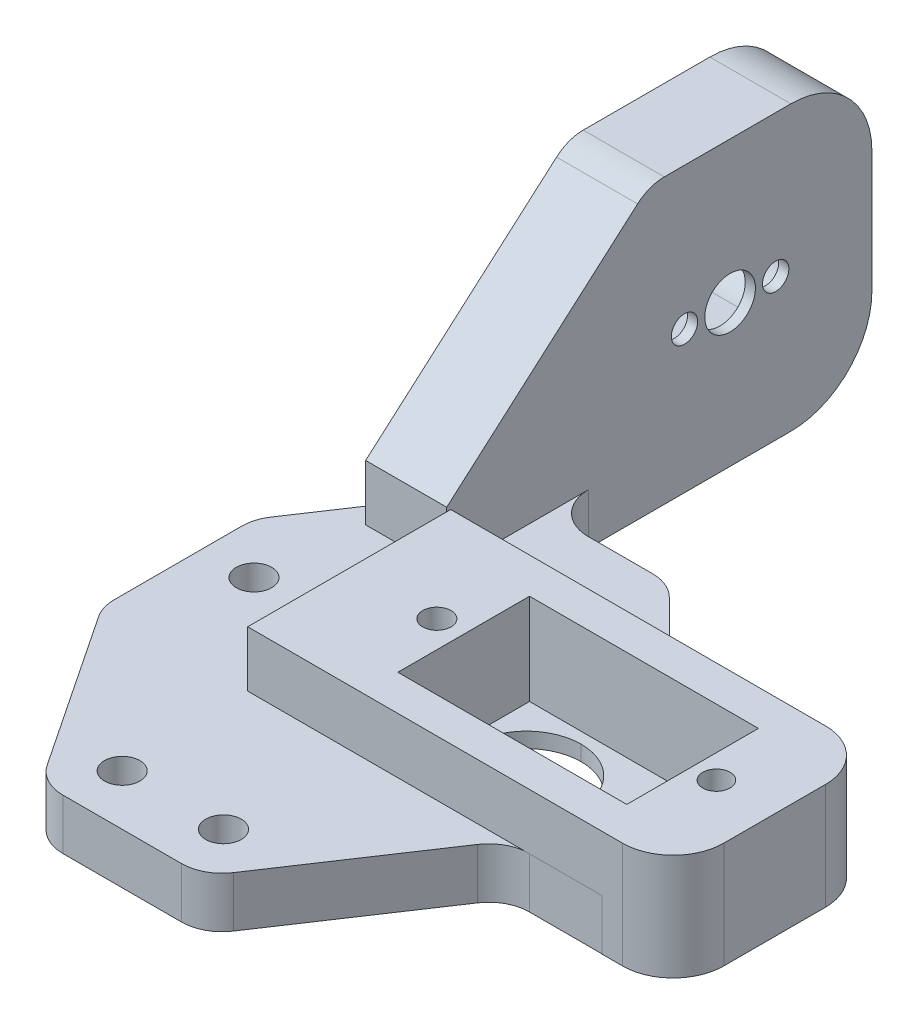
SolidWorks part; units mm, degrees
ref_plane "Front Plane" through (0, 0, 0) normal (0, 0, 1) x (1, 0, 0)
ref_plane "Top Plane" through (0, 0, 0) normal (0, 1, 0) x (1, 0, 0)
ref_plane "Right Plane" through (0, 0, 0) normal (1, 0, 0) x (0, 0, -1)
sketch "Sketch1" plane through (0, 0, 0) normal (0, 1, 0) x (1, 0, 0)
  line L0 (0, 0) -> (45, 0) construction
  line L1 (45, -10) -> (45, 10)
  line L2 (45, 10) -> (21, 10)
  line L3 (21, 10) -> (11.0015, 19.9985)
  line L4 (11.0015, 19.9985) -> (-4.9985, 19.9985)
  line L5 (-4.9985, 19.9985) -> (-14.9997, 4.9966)
  line L6 (-14.9997, 4.9966) -> (-14.9997, -10.0034)
  line L10 (-14.9997, -10.0034) -> (-2.9797, -28.0334)
  line L11 (-2.9797, -28.0334) -> (13.0203, -28.0334)
  line L16 (13.0203, -28.0334) -> (25.0425, -10)
  line L17 (25.0425, -10) -> (45, -10)
  point P6 (45, 0)
  dimension "D1" = 20
  dimension "D2" = 24
  dimension "D3" = 14.14
  dimension "D4" = 16
  dimension "D5" = 18.03
  dimension "D6" = 15
  dimension "D7" = 146.31
  dimension "D8" = 123.69
  dimension "D9" = 18.03
  dimension "D10" = 16
  dimension "D11" = 123.69
  dimension "D13" = 225
  dimension "D14" = 45
extrude "Boss-Extrude1" add sketch "Sketch1" along normal blind 5
sketch "Sketch2" plane through (0, 5, 0) normal (0, 1, 0) x (1, 0, 0)
  line L0 (45, 0) -> (-25.8429, 0) construction
  line L1 (45, -10) -> (45, 10) construction
  line L2 (-14.9997, 4.9966) -> (-14.9997, -10.0034) construction
  line L3 (-14.9997, -10.0034) -> (25.0425, -10) construction
  line L4 (5.0214, -10.0017) -> (5.0214, -23.0334) construction
  line L5 (10.0214, -23.0334) -> (0.0214, -23.0334)
  line L6 (-2.9797, -28.0334) -> (13.0203, -28.0334) construction
  line L8 (11.5, -5.4) -> (22.3, -5.4)
  line L9 (11.5, -5.4) -> (11.5, 5.4)
  line L10 (11.5, 5.4) -> (22.3, 5.4)
  line L11 (22.3, -5.4) -> (22.3, 5.4)
  line L12 (11.5, -5.4) -> (22.3, 5.4) construction
  line L13 (11.5, 5.4) -> (22.3, -5.4) construction
  circle A0 centre (-9.9997, 0) radius 1.75
  circle A1 centre (0.0214, -23.0334) radius 1.75
  circle A2 centre (10.0214, -23.0334) radius 1.75
  point P18 (5.0214, -23.0334)
  point P22 (16.9, 0)
  dimension "D2" = 3.5
  dimension "D5" = 3.5
  dimension "D1" = 5
  dimension "D3" = 10
  dimension "D4" = 5
  dimension "D6" = 22.7
  dimension "D7" = 10.8
  dimension "D8" = 10.8
extrude "Cut-Extrude1" cut sketch "Sketch2" against normal through all contours L8 L11 L10 L9 | A0 | A1 | A2 region at (-1.6791, 5, 23.0334) region at (10.0214, 5, 21.3329) region at (16.9, 5, 0) region at (-9.9997, 5, 0)
fillet "Fillet1" 2 edges at (11.5, 2.5, -5.4) (11.5, 2.5, 5.4) type full round first side face at (16.9, 2.5, -5.4) second side face at (16.9, 2.5, 5.4) middle face at (11.5, 2.5, 0)
fillet "Fillet2" 2 edges at (22.3, 2.5, -5.4) (22.3, 2.5, 5.4) type full round first side face at (19.6, 2.5, -5.4) second side face at (19.6, 2.5, 5.4) middle face at (22.3, 2.5, 0)
fillet "Fillet3" 2 edges at (45, 2.5, -10) (45, 2.5, 10) type full round first side face at (33, 2.5, -10) second side face at (35.0212, 2.5, 10) middle face at (45, 2.5, 0)
sketch "Sketch6" plane through (0, 5, 0) normal (0, 1, 0) x (1, 0, 0)
  line L0 (11.5, 0) -> (22.3, 0) construction
  line L2 (5.4, -6.5) -> (28.4, -6.5)
  line L3 (5.4, -6.5) -> (5.4, 6.5)
  line L4 (5.4, 6.5) -> (28.4, 6.5)
  line L5 (28.4, -6.5) -> (28.4, 6.5)
  line L6 (5.4, -6.5) -> (28.4, 6.5) construction
  line L7 (5.4, 6.5) -> (28.4, -6.5) construction
  line L8 (-0.6, -10.0211) -> (34.4, -10.0211)
  line L9 (-0.6, -10.0211) -> (-0.6, 10.0211)
  line L10 (-0.6, 10.0211) -> (34.4, 10.0211)
  line L11 (34.4, -10.0211) -> (34.4, 10.0211)
  line L12 (-0.6, -10.0211) -> (34.4, 10.0211) construction
  line L13 (-0.6, 10.0211) -> (34.4, -10.0211) construction
  arc A0 (16.9, 5.4) -> (16.9, -5.4) centre (16.9, 0) ccw construction
  arc A1 (16.9, -5.4) -> (16.9, 5.4) centre (16.9, 0) ccw construction
  point P8 (16.9, 0)
  point P13 (16.9, 0)
  dimension "D1" = 6
  dimension "D2" = 13
  dimension "D3" = 23
extrude "Boss-Extrude3" add sketch "Sketch6" along normal blind 5.5
sketch "Sketch7" plane through (0, 5, 0) normal (0, 1, 0) x (1, 0, 0)
  line L4 (5.4, 6.5) -> (5.4, -6.5)
  line L5 (5.4, -6.5) -> (28.4, -6.5)
  line L6 (28.4, -6.5) -> (28.4, 6.5)
  line L7 (28.4, 6.5) -> (5.4, 6.5)
  line L8 (5.4, 6.5) -> (5.4, -6.5)
  line L9 (5.4, -6.5) -> (28.4, -6.5)
  line L10 (28.4, -6.5) -> (28.4, 6.5)
  line L11 (28.4, 6.5) -> (5.4, 6.5)
  dimension "D1" = 0
extrude "Cut-Extrude3" cut sketch "Sketch7" against normal blind 3.5
sketch "Sketch8" plane through (0, 5, 0) normal (0, 1, 0) x (1, 0, 0)
  line L3 (34.4, 10) -> (34.4, -10)
  line L4 (34.4, -10) -> (35, -10)
  line L5 (35, 10) -> (34.4, 10)
  line L6 (34.4, 10) -> (34.4, -10)
  line L7 (34.4, -10) -> (35, -10)
  line L8 (35, 10) -> (34.4, 10)
  arc A1 (35, -10) -> (35, 10) centre (35, 0) ccw
  arc A2 (35, -10) -> (35, 10) centre (35, 0) ccw
  dimension "D1" = 0
extrude "Cut-Extrude4" cut sketch "Sketch8" against normal through all body kept at (25.0425, 0, 10)
sketch "Sketch9" plane through (0, 0, -19.9985) normal (0, 0, -1) x (-1, 0, 0)
  line L0 (-11.0015, 0) -> (4.9985, 0) construction
  line L1 (0.9985, 0) -> (8.9985, 0)
  line L2 (0.9985, 0) -> (0.9985, 28)
  line L3 (0.9985, 28) -> (8.9985, 28)
  line L4 (8.9985, 0) -> (8.9985, 28)
  line L5 (4.9985, 5) -> (4.9985, 0) construction
  dimension "D1" = 4
  dimension "D2" = 4
  dimension "D3" = 28
extrude "Boss-Extrude4" add sketch "Sketch9" along normal blind 32
sketch "Sketch11" plane through (-0.9985, 0, 0) normal (1, 0, 0) x (0, 0, -1)
  line L0 (10, 0) -> (19.9985, 0) construction
  line L1 (51.9985, 28) -> (51.9985, 0) construction
  line L2 (42.4985, 14) -> (33.4985, 14) construction
  circle A0 centre (37.9985, 14) radius 2.5
  circle A1 centre (33.4985, 14) radius 1.3
  circle A2 centre (42.4985, 14) radius 1.3
  point P9 (37.9985, 14)
  dimension "D1" = 5
  dimension "D5" = 2.6
  dimension "D2" = 14
  dimension "D3" = 14
  dimension "D4" = 9
extrude "Cut-Extrude5" cut sketch "Sketch11" against normal through all
fillet "Fillet6" radius 8 2 edges at (-4.9985, 0, -51.9985) (-4.9985, 28, -51.9985)
sketch "Sketch12" plane through (-8.9985, 0, 0) normal (-1, 0, 0) x (0, 0, 1)
  line L0 (-10.0211, 10.5) -> (-19.9985, 28)
  line L1 (-19.9985, 28) -> (-19.9985, 0)
  line L2 (-19.9985, 0) -> (-10, 0)
  line L3 (-10, 0) -> (-10.0211, 10.5)
extrude "Boss-Extrude5" add sketch "Sketch12" against normal up to surface (8 mm away) up to face at (-0.9985, 14, -43.7985)
sketch "Sketch13" plane through (-8.9985, 0, 0) normal (-1, 0, 0) x (0, 0, 1)
  line L0 (-40.4985, 14) -> (-35.4985, 14) construction
  line L2 (-44.9985, 10.5) -> (-30.9985, 10.5)
  line L3 (-44.9985, 10.5) -> (-44.9985, 17.5)
  line L4 (-44.9985, 17.5) -> (-30.9985, 17.5)
  line L5 (-30.9985, 10.5) -> (-30.9985, 17.5)
  line L6 (-44.9985, 10.5) -> (-30.9985, 17.5) construction
  line L7 (-44.9985, 17.5) -> (-30.9985, 10.5) construction
  circle A0 centre (-37.9985, 14) radius 2.5 construction
  point P5 (-37.9985, 14)
  dimension "D1" = 7
  dimension "D2" = 14
extrude "Cut-Extrude6" cut sketch "Sketch13" against normal blind 7
fillet "Fillet7" 2 edges at (-5.4985, 17.5, -44.9985) (-5.4985, 10.5, -44.9985) type full round first side face at (-5.4985, 17.5, -37.9985) second side face at (-5.4985, 10.5, -37.9985) middle face at (-5.4985, 14, -44.9985)
fillet "Fillet8" 2 edges at (-5.4985, 17.5, -30.9985) (-5.4985, 10.5, -30.9985) type full round first side face at (-5.4985, 17.5, -36.2485) second side face at (-5.4985, 10.5, -36.2485) middle face at (-5.4985, 14, -30.9985)
sketch "Sketch14" plane through (-8.9985, 0, 0) normal (-1, 0, 0) x (0, 0, 1)
  line L0 (-10.0211, 10.5) -> (-29.9985, 28)
  line L1 (-43.9985, 28) -> (-19.9985, 28) construction
  line L2 (-29.9985, 28) -> (-19.9985, 28)
  line L3 (-19.9985, 28) -> (-10.0211, 10.5)
  dimension "D1" = 10
extrude "Cut-Extrude7" cut sketch "Sketch14" against normal through all
fillet "Fillet9" radius 4 10 edges at (-0.9985, 2.5, -19.9985) (11.0015, 2.5, -19.9985) (21, 2.5, -10) (25.0425, 2.5, 10) (13.0203, 2.5, 28.0334) (-2.9797, 2.5, 28.0334) (-14.9997, 2.5, 10.0034) (-14.9997, 2.5, -4.9966) (-8.9985, 2.5, -13.9985) (-4.9985, 28, -29.9985)
sketch "Sketch15" plane through (0, 1.5, 0) normal (0, 1, 0) x (1, 0, 0)
  line L0 (5.4, -6.5) -> (28.4, -6.5) construction
  line L1 (5.4, 6.5) -> (10.7, 6.5)
  line L2 (5.4, 6.5) -> (5.4, -6.5)
  line L3 (5.4, -6.5) -> (10.7, -6.5)
  line L4 (10.7, 6.5) -> (10.7, -6.5)
  line L5 (5.4, 0) -> (10.7, 0) construction
  circle A0 centre (8.05, 0) radius 1.4
  dimension "D2" = 2.8
  dimension "D1" = 5.3
extrude "Boss-Extrude6" add sketch "Sketch15" along normal up to surface (9 mm away) up to face at (16.9, 10.5, 0)
sketch "Sketch16" plane through (0, 10.5, 0) normal (0, 1, 0) x (1, 0, 0)
  line L0 (34.4, 10.0211) -> (41.4, 10.0211)
  line L1 (34.4, -10.0211) -> (41.4, -10.0211)
  line L2 (41.4, -10.0211) -> (41.4, 10.0211)
  line L3 (34.4, -10.0211) -> (34.4, 10.0211) construction
  line L4 (34.4, -10.0211) -> (34.4, 10.0211)
  dimension "D1" = 7
extrude "Boss-Extrude7" add sketch "Sketch16" against normal up to surface (10.5 mm away) up to face at (5.3358, 0, -3.5695)
sketch "Sketch17" plane through (0, 10.5, 0) normal (0, 1, 0) x (1, 0, 0)
  line L0 (8.05, 0) -> (35.65, 0) construction
  circle A0 centre (35.65, 0) radius 1.35
  dimension "D2" = 2.7
  dimension "D1" = 27.6
extrude "Cut-Extrude8" cut sketch "Sketch17" against normal up to surface (9 mm away) up to face at (8.05, 1.5, 1.4)
fillet "Fillet10" radius 5 2 edges at (41.4, 5.25, 10.0211) (41.4, 5.25, -10.0211)
sketch "Sketch18" plane through (0, 10.5, 0) normal (0, 1, 0) x (1, 0, 0)
  line L0 (10.7, -6.5) -> (28.4, -6.5) construction
  line L1 (28.4, 6.5) -> (33.3, 6.5)
  line L2 (28.4, 6.5) -> (28.4, -6.5)
  line L3 (28.4, -6.5) -> (33.3, -6.5)
  line L4 (33.3, 6.5) -> (33.3, -6.5)
  dimension "D1" = 4.9
extrude "Cut-Extrude9" cut sketch "Sketch18" against normal up to surface (9 mm away) up to face at (16.9, 1.5, 0)
